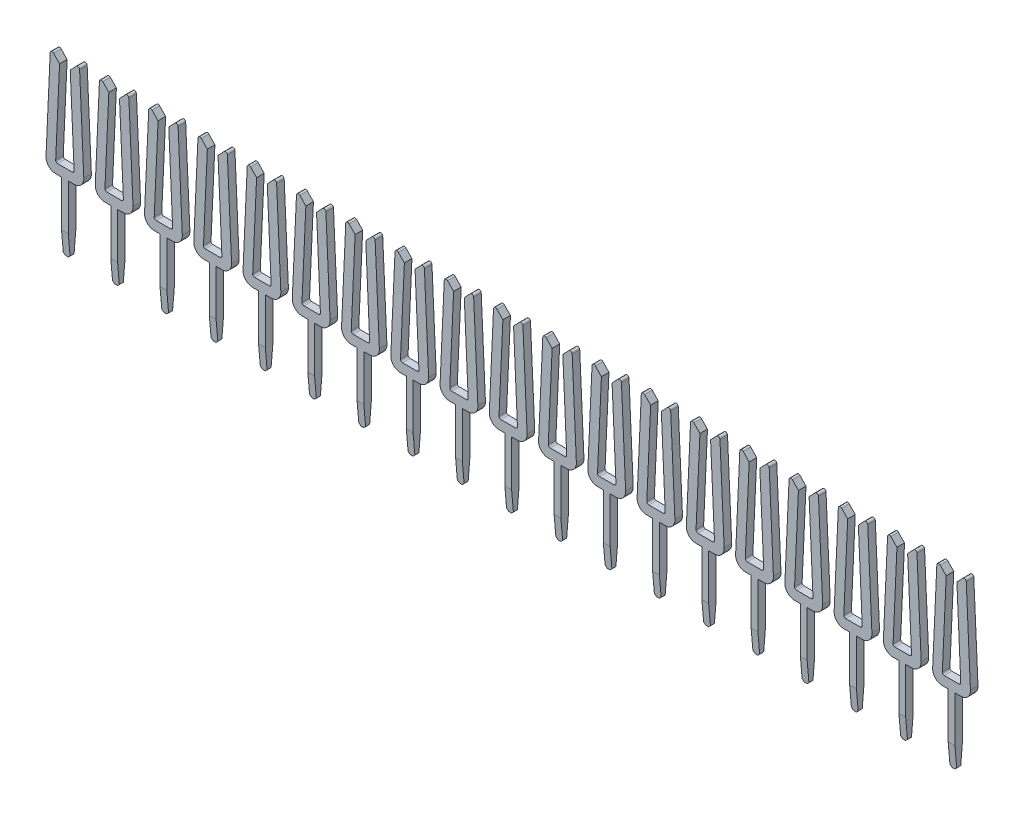
SolidWorks part; units mm, degrees
other "Шпилька"
ref_plane "Front Plane" through (0, 0, 0) normal (0, 0, 1) x (1, 0, 0)
ref_plane "Top Plane" through (0, 0, 0) normal (0, 1, 0) x (1, 0, 0)
ref_plane "Right Plane" through (0, 0, 0) normal (1, 0, 0) x (0, 0, -1)
sketch "Эскиз-Шпилька" plane through (0, 0, 0) normal (0, 0, 1) x (1, 0, 0)
  line L0 (-0.2751, 4.5045) -> (-0.586, 4.8299)
  line L1 (-0.7582, 4.7653) -> (-0.9745, 0.0228)
  line L2 (-0.475, -0.5) -> (-0.175, -0.5)
  line L3 (-0.175, -0.5) -> (-0.175, -3.9)
  line L4 (-0.175, -3.9) -> (-0.075, -4)
  line L5 (0, 4.5045) -> (0, -4) construction
  line L6 (-0.375, 0) -> (0.375, 0)
  line L7 (-0.4749, 0.1045) -> (-0.2751, 4.5045)
  line L8 (0.4749, 0.1045) -> (0.2751, 4.5045)
  line L9 (0.175, -3.9) -> (0.075, -4)
  line L10 (0.175, -0.5) -> (0.175, -3.9)
  line L11 (0.475, -0.5) -> (0.175, -0.5)
  line L12 (0.7582, 4.7653) -> (0.9745, 0.0228)
  line L13 (0.2751, 4.5045) -> (0.586, 4.8299)
  line L14 (-0.075, -4) -> (0.075, -4)
  arc A0 (-0.9745, 0.0228) -> (-0.475, -0.5) centre (-0.475, 0) ccw
  arc A1 (-0.4749, 0.1045) -> (-0.375, 0) centre (-0.375, 0.1) ccw
  arc A2 (-0.586, 4.8299) -> (-0.7582, 4.7653) centre (-0.6583, 4.7608) ccw
  arc A3 (0.586, 4.8299) -> (0.7582, 4.7653) centre (0.6583, 4.7608) cw
  arc A4 (0.4749, 0.1045) -> (0.375, 0) centre (0.375, 0.1) cw
  arc A5 (0.9745, 0.0228) -> (0.475, -0.5) centre (0.475, 0) cw
  point P26 (0, 0)
  point P29 (0, 0)
  point P30 (0, 0)
  point P31 (0, 0)
  point P32 (0, 0)
  point P33 (0, 0)
  point P34 (0, 0)
  point P35 (0, 0)
  point P37 (0, -4)
  dimension "D1" = 2.6
  dimension "D2" = 0.1
  dimension "D6" = 0.1
  dimension "D8" = 0.5
  dimension "D3" = 0.45
  dimension "D4" = 133.7
  dimension "D5" = 4.4
  dimension "D7" = 0.375
  dimension "D9" = 0.3
  dimension "D10" = 3.5
  dimension "D11" = 0.1
  dimension "D12" = 0.1
  dimension "D13" = 0.35
  dimension "D14" = 0.5
extrude "Бобышка-Шпилька" add sketch "Эскиз-Шпилька" along normal blind 0.195 and the other way blind 0.195
chamfer "Фаска1" distance 0.1 angle 85 1 edges at (0, -4, 0.195) first distance on face at (0, -4, 0)
chamfer "Фаска2" distance 0.1 angle 85 1 edges at (0, -4, -0.195) first distance on face at (0, -4, -0.05)
pattern_linear "Линейный массив1" count 19 spacing 2.54 along (-1, 0, 0) of "Бобышка-Шпилька"
